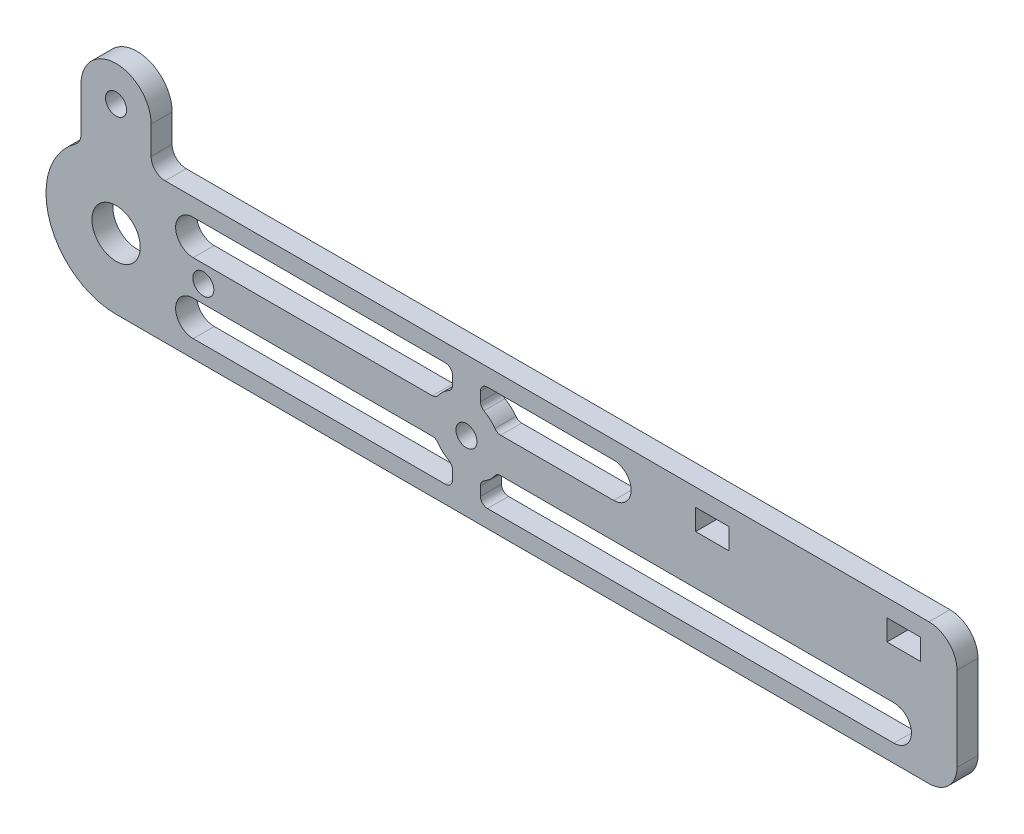
SolidWorks part; units mm, degrees
ref_plane "Front Plane" through (0, 0, 0) normal (0, 0, 1) x (1, 0, 0)
ref_plane "Top Plane" through (0, 0, 0) normal (0, 1, 0) x (1, 0, 0)
ref_plane "Right Plane" through (0, 0, 0) normal (1, 0, 0) x (0, 0, -1)
sketch "Sketch1" plane through (0, 0, 0) normal (0, 0, 1) x (1, 0, 0)
  line L0 (0, 0) -> (120, 0) construction
  line L1 (0, 10) -> (120, 10)
  line L2 (0, -10) -> (120, -10)
  line L3 (0, 0) -> (14.45, 0) construction
  line L4 (120, 10) -> (120, -10)
  arc A5 (0, 10) -> (0, -10) centre (0, 0) ccw
  point P3 (60, 0)
  point P11 (120, 0)
  dimension "D2" = 120
  dimension "D3" = 20
extrude "Boss-Extrude1" add sketch "Sketch1" along normal blind 3
sketch "Sketch2" plane through (0, 0, 3) normal (0, 0, 1) x (1, 0, 0)
  circle A0 centre (0, 0) radius 3.45 construction
  circle A1 centre (0, 0) radius 3.45
extrude "Cut-Extrude1" cut sketch "Sketch2" against normal up to next
fillet "Fillet1" radius 4 2 edges at (120, -10, 1.5) (120, 10, 1.5)
sketch "Sketch3" plane through (0, 0, 3) normal (0, 0, 1) x (1, 0, 0)
  line L0 (82.7, 4.5) -> (82.7, 7.5) construction
  line L1 (87.5, 4.5) -> (87.5, 7.5) construction
  line L2 (87.5, 4.5) -> (82.7, 4.5) construction
  line L3 (87.5, 7.5) -> (82.7, 7.5) construction
  line L4 (82.7, 4.5) -> (82.7, 7.5)
  line L5 (87.5, 4.5) -> (87.5, 7.5)
  line L6 (87.5, 4.5) -> (82.7, 4.5)
  line L7 (87.5, 7.5) -> (82.7, 7.5)
  line L12 (114.8, 7.5) -> (110, 7.5)
  line L13 (110, 7.5) -> (110, 4.5)
  line L14 (110, 4.5) -> (114.8, 4.5)
  line L15 (114.8, 4.5) -> (114.8, 7.5)
  line L16 (114.8, 7.5) -> (110, 7.5)
  line L17 (110, 7.5) -> (110, 4.5)
  line L18 (110, 4.5) -> (114.8, 4.5)
  line L19 (114.8, 4.5) -> (114.8, 7.5)
  dimension "D1" = 0
extrude "Cut-Extrude2" cut sketch "Sketch3" against normal up to next
sketch "Sketch4" plane through (0, 0, 3) normal (0, 0, 1) x (1, 0, 0)
  line L0 (0, 0) -> (120, 0) construction
  line L1 (120, -6) -> (120, 6) construction
  line L2 (11, 5) -> (71, 5) construction
  line L3 (11, 7.5) -> (71, 7.5)
  line L4 (11, 2.5) -> (71, 2.5)
  line L5 (11, -5) -> (111, -5) construction
  line L6 (11, -2.5) -> (111, -2.5)
  line L7 (11, -7.5) -> (111, -7.5)
  line L8 (11, 5) -> (11, -5) construction
  arc A0 (11, 7.5) -> (11, 2.5) centre (11, 5) ccw
  arc A1 (71, 2.5) -> (71, 7.5) centre (71, 5) ccw
  arc A2 (11, -2.5) -> (11, -7.5) centre (11, -5) ccw
  arc A3 (111, -7.5) -> (111, -2.5) centre (111, -5) ccw
  point P7 (41, 5)
  point P14 (61, -5)
  dimension "D3" = 2.5
  dimension "D4" = 2.5
  dimension "D1" = 5
  dimension "D2" = 5
  dimension "D5" = 60
  dimension "D6" = 100
  dimension "D7" = 11
extrude "Cut-Extrude3" cut sketch "Sketch4" against normal up to next
sketch "Sketch5" plane through (0, 0, 3) normal (0, 0, 1) x (1, 0, 0)
  line L0 (0, 0) -> (50, 0) construction
  line L1 (50, 7.5) -> (50, -7.5) construction
  line L2 (11, -7.5) -> (111, -7.5) construction
  line L3 (48, 7.5) -> (48, 4.5826)
  line L4 (52, 7.5) -> (52, 4.5826)
  line L5 (48, 7.5) -> (52, 7.5)
  line L6 (52, -7.5) -> (48, -7.5)
  line L7 (48, -4.5826) -> (48, -7.5)
  line L8 (48, 7.5) -> (48, -7.5) construction
  line L9 (52, -4.5826) -> (52, -7.5)
  line L10 (52, 7.5) -> (52, -7.5) construction
  arc A0 (48, 4.5826) -> (48, -4.5826) centre (50, 0) ccw
  arc A1 (52, -4.5826) -> (52, 4.5826) centre (50, 0) ccw
  circle A2 centre (50, 0) radius 1.5
  point P9 (50, 0)
  line M9 (11, 7.5) -> (71, 7.5)
  line M11 (71, 2.5) -> (11, 2.5)
  line M13 (11, -2.5) -> (111, -2.5)
  line M15 (111, -7.5) -> (11, -7.5)
  dimension "D2" = 10
  dimension "D5" = 3
  dimension "D1" = 50
  dimension "D3" = 2
  dimension "D4" = 2
extrude "Boss-Extrude2" add sketch "Sketch5" against normal up to surface (3 mm away) contours A1 L4 L3 A0 M11 M9 | L9 A1 A0 L7 M13 M15 | A1 A0 A2 M13 M11 region at (50, 4.6056, 3) region at (50, 2.3882, 3) region at (50, -4.6056, 3) up to face at (41, 5, 0)
extrude "Cut-Extrude4" cut sketch "Sketch5<3>" against normal up to next contours A2 region at (50, 0, 3)
sketch "Sketch5<3>" plane through (0, 0, 3) normal (0, 0, 1) x (1, 0, 0) same geometry as "Sketch5"
fillet "Fillet2" radius 1 12 edges at (52, -4.5826, 1.5) (52, -7.5, 1.5) (54.3301, -2.5, 1.5) (48, -4.5826, 1.5) (48, -7.5, 1.5) (45.6699, -2.5, 1.5) (48, 4.5826, 1.5) (45.6699, 2.5, 1.5) (48, 7.5, 1.5) (52, 7.5, 1.5) (52, 4.5826, 1.5) (54.3301, 2.5, 1.5)
sketch "Sketch6" plane through (0, 0, 0) normal (0, 0, -1) x (-1, 0, 0)
  circle A0 centre (-12.45, 0) radius 1.5
  dimension "D1" = 3
extrude "Cut-Extrude5" cut sketch "Sketch6" against normal up to next
sketch "Sketch8" plane through (0, 0, 3) normal (0, 0, 1) x (1, 0, 0)
  line L0 (0, 0) -> (0, 10) construction
  line L1 (0, 10) -> (0, 16) construction
  line L2 (5, 16) -> (5, 10)
  line L3 (116, 10) -> (0, 10) construction
  line L4 (-5, 16) -> (-5, 8.6603)
  line L5 (5, 10) -> (0, 10)
  arc A0 (0, 10) -> (0, -10) centre (0, 0) ccw construction
  arc A1 (5, 16) -> (-5, 16) centre (0, 16) ccw
  circle A2 centre (0, 16) radius 1.5
  arc A4 (0, 10) -> (-5, 8.6603) centre (0, 0) ccw
  dimension "D1" = 10
  dimension "D2" = 3
  dimension "D3" = 6
extrude "Boss-Extrude3" add sketch "Sketch8" against normal up to surface (3 mm away) up to face at (10.95, 0, 0)
fillet "Fillet3" radius 2 2 edges at (-5, 8.6603, 1.5) (5, 10, 1.5)
